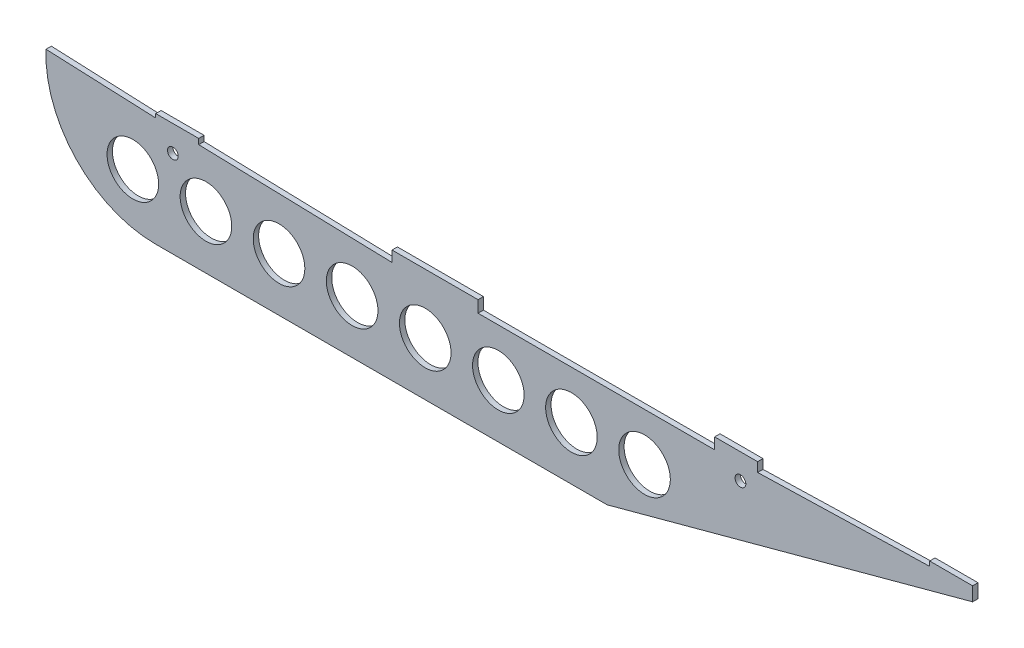
SolidWorks part; units mm, degrees
material "Birch Ply"
ref_plane "Front Plane"
ref_plane "Top Plane" through (0, 0, 0) normal (0, 1, 0) x (1, 0, 0)
ref_plane "Right Plane"
sketch "Sketch1" plane through (0, 0, 0) normal (0, 0, 1) x (1, 0, 0)
  line L1 (331.4792, -67.3278) -> (547.3792, -9.0155)
  line L2 (0, 0) -> (-2.5762, -60.2421) construction
  line L3 (547.3792, -0.8036) -> (547.3792, -9.0155)
  line L4 (547.3792, -0.8036) -> (521.9792, -0.8036)
  line L5 (521.9792, -0.8036) -> (521.9792, -3.5503)
  line L6 (521.9792, -3.5503) -> (420.3792, -6.318)
  line L7 (420.3792, -6.318) -> (420.3792, -0.8036)
  line L8 (420.3792, -0.8036) -> (394.9792, -0.8036)
  line L9 (394.9792, -0.8036) -> (394.9792, -7.4329)
  line L10 (394.9792, -7.4329) -> (255.2141, -7.4329)
  line L11 (255.2141, -7.4329) -> (255.2141, -0.5036)
  line L12 (255.2141, -0.5036) -> (204.4141, -0.5036)
  line L13 (204.4141, -0.5036) -> (204.4141, -6.8758)
  line L14 (331.4792, -67.3278) -> (64.5102, -67.3278)
  line L15 (204.4141, -6.8758) -> (90.2232, -3.7073)
  line L16 (90.2232, -3.7073) -> (90.2232, -0.5036)
  line L18 (90.2232, -0.5036) -> (64.8232, -0.5036)
  line L19 (64.8232, -0.5036) -> (64.8232, -2.7721)
  line L20 (64.8232, -2.7721) -> (0, 0)
  arc A0 (0, 0) -> (64.5102, -67.3278) centre (64.5102, -2.7587) ccw
  dimension "D19" = 2.7587
  dimension "D2" = 25.4
  dimension "D3" = 25.4
  dimension "D4" = 50.8
  dimension "D5" = 139.7652
  dimension "D6" = 114.2348
  dimension "D7" = 101.6
  dimension "D8" = 25.4
  dimension "D9" = 3.2036
  dimension "D10" = 6.3722
  dimension "D11" = 6.9293
  dimension "D12" = 6.6293
  dimension "D13" = 5.5145
  dimension "D14" = 2.7467
  dimension "D15" = 215.9
  dimension "D16" = 64.8232
  dimension "D17" = 66.8242
  dimension "D18" = 2.2684
  dimension "D22" = 58.3123
extrude "Boss-Extrude1" add sketch "Sketch1" along normal blind 1.5875 and the other way blind 1.5875 contours L15 L16 L18 L19 L20 A0 L14 L1 L3 L4 L5 L6 L7 L8 L9 L10 L11 L12 L13
sketch "Sketch2" plane through (0, 0, 0) normal (0, 0, 1) x (1, 0, 0)
  line L0 (420.3792, -0.8036) -> (394.9792, -0.8036) construction
  line L4 (547.3792, -0.8036) -> (547.3792, -9.0155) construction
  line L5 (90.2232, -0.5036) -> (64.8232, -0.5036) construction
  circle A0 centre (410.2192, -15.7436) radius 3.175
  circle A5 centre (74.9392, -15.7436) radius 3.175
  dimension "D1" = 6.35
  dimension "D4" = 472.44
  dimension "D10" = 6.35
  dimension "D2" = 14.94
  dimension "D5" = 15.24
  dimension "D3" = 137.16
extrude "Cut-Extrude1" cut sketch "Sketch2" along normal through all and the other way through all contours A0 | A5
sketch "Sketch3" plane through (0, 0, 0) normal (0, 0, 1) x (1, 0, 0)
  line L0 (353.5628, -35.7109) -> (51.3028, -35.7109) construction
  line L3 (360.0202, -59.6192) -> (357.5366, -50.4237) construction
  line L4 (331.4792, -67.3278) -> (547.3792, -9.0155) construction
  line L5 (83.8227, -24.8197) -> (77.1601, -18.0126) construction
  circle A0 centre (51.3028, -35.7109) radius 15.24
  circle A2 centre (94.4828, -35.7109) radius 15.24
  circle A3 centre (137.6628, -35.7109) radius 15.24
  circle A4 centre (180.8428, -35.7109) radius 15.24
  circle A5 centre (224.0228, -35.7109) radius 15.24
  circle A6 centre (267.2028, -35.7109) radius 15.24
  circle A7 centre (310.3828, -35.7109) radius 15.24
  circle A8 centre (353.5628, -35.7109) radius 15.24
  circle A10 centre (74.9392, -15.7436) radius 3.175 construction
  dimension "D2" = 30.48
  dimension "D1" = 30.48
  dimension "D3" = 30.48
  dimension "D4" = 30.48
  dimension "D5" = 30.48
  dimension "D6" = 30.48
  dimension "D7" = 30.48
  dimension "D8" = 43.18
  dimension "D9" = 30.48
  dimension "D11" = 9.525
  dimension "D20" = 43.18
  dimension "D21" = 43.18
  dimension "D22" = 43.18
  dimension "D23" = 43.18
  dimension "D24" = 43.18
  dimension "D25" = 43.18
  dimension "D10" = 9.525
extrude "Cut-Extrude2" cut sketch "Sketch3" against normal blind 2.54 and the other way blind 2.54 contours L0 A2 | A2 L0 | L0 A8 | A0 | A3 | A4 | A5 | A6 | A7 | A8 region at (94.4828, -35.7109, 0) region at (353.5628, -35.7109, 0)
